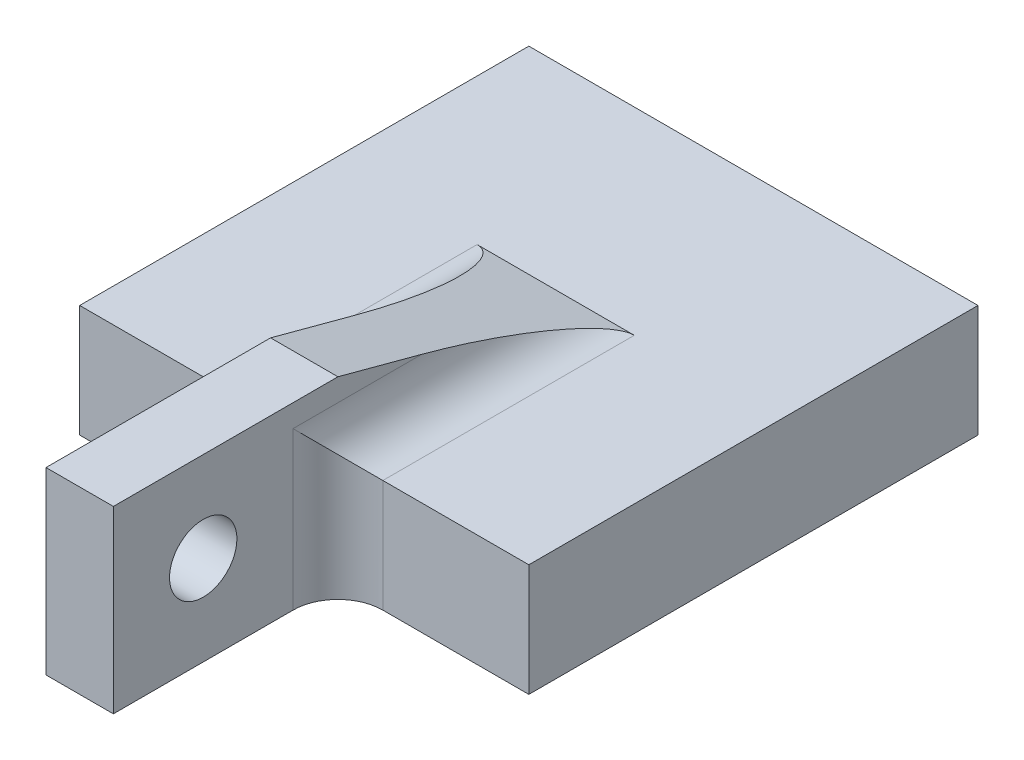
SolidWorks part; units mm, degrees
ref_plane "Front Plane" through (0, 0, 0) normal (0, 0, 1) x (1, 0, 0)
ref_plane "Top Plane" through (0, 0, 0) normal (0, 1, 0) x (1, 0, 0)
ref_plane "Right Plane" through (0, 0, 0) normal (1, 0, 0) x (0, 0, -1)
sketch "Sketch1" plane through (0, 0, 0) normal (0, 1, 0) x (1, 0, 0)
  line L1 (-10, -10) -> (10, -10)
  line L2 (-10, -10) -> (-10, 10)
  line L3 (-10, 10) -> (10, 10)
  line L4 (10, -10) -> (10, 10)
  line L5 (-10, -10) -> (10, 10) construction
  line L6 (-10, 10) -> (10, -10) construction
  point P0 (0, 0)
  dimension "D1" = 20
extrude "Boss-Extrude1" add sketch "Sketch1" along normal blind 5
sketch "Sketch2" plane through (0, 0, 10) normal (0, 0, 1) x (1, 0, 0)
  line L0 (-10, 0) -> (10, 0) construction
  line L1 (-1.5, 8) -> (1.5, 8)
  line L2 (-1.5, 8) -> (-1.5, 0)
  line L3 (-1.5, 0) -> (1.5, 0)
  line L4 (1.5, 8) -> (1.5, 0)
  line L5 (-1.5, 8) -> (1.5, 0) construction
  line L6 (-1.5, 0) -> (1.5, 8) construction
  point P0 (0, 4)
  point P7 (0, 0)
  dimension "D1" = 3
  dimension "D2" = 8
extrude "Boss-Extrude2" add sketch "Sketch2" along normal blind 10
sketch "Sketch3" plane through (1.5, 0, 0) normal (1, 0, 0) x (0, 0, -1)
  line L0 (-20, 0) -> (-20, 8) construction
  circle A0 centre (-16, 4) radius 1.5
  point P2 (0, 0)
  point P5 (-20, 4)
  dimension "D2" = 3
  dimension "D1" = 4
extrude "Cut-Extrude1" cut sketch "Sketch3" against normal through all
chamfer "Chamfer1" distance 3 angle 75 1 edges at (0, 5, 10) first distance on face at (0, 6.5, 10)
fillet "Fillet1" radius 2 4 edges at (1.5, 5, 4.4019) (-1.5, 5, 4.4019) (1.5, 2.5, 10) (-1.5, 2.5, 10)
